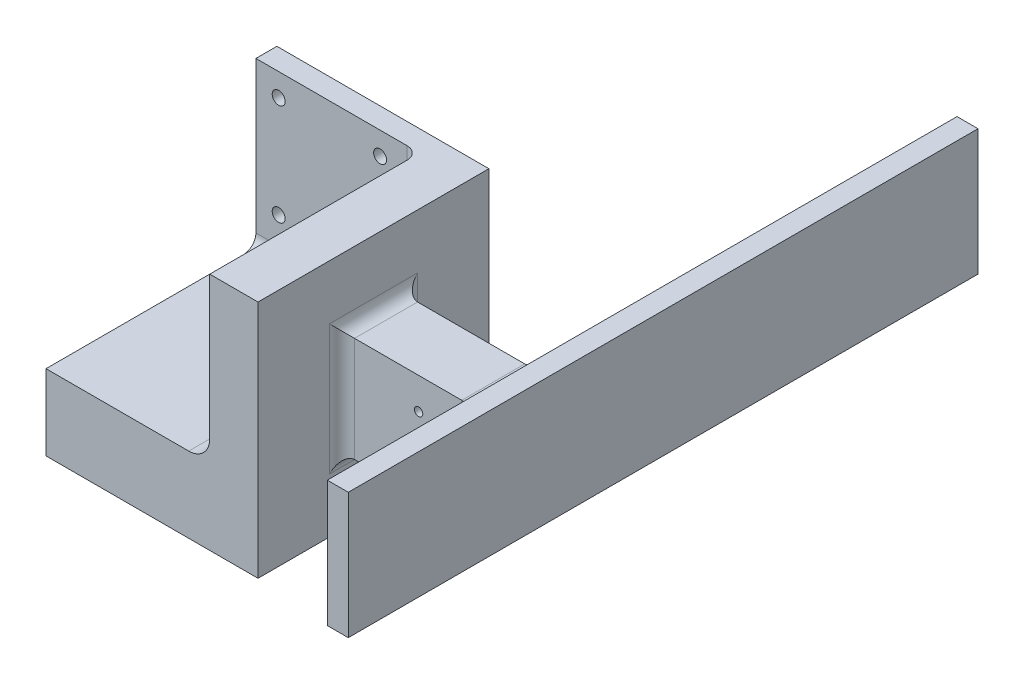
SolidWorks part; units mm, degrees
ref_plane "Front Plane" through (0, 0, 0) normal (0, 0, 1) x (1, 0, 0)
ref_plane "Top Plane" through (0, 0, 0) normal (0, 1, 0) x (1, 0, 0)
ref_plane "Right Plane" through (0, 0, 0) normal (1, 0, 0) x (0, 0, -1)
sketch "Sketch1" plane through (0, 0, 0) normal (0, 0, 1) x (1, 0, 0)
  line L0 (0, 36.3302) -> (0, -35.4873) construction
  line L1 (-17.5, 17.5) -> (17.5, 17.5)
  line L2 (-17.5, 17.5) -> (-17.5, -17.5)
  line L5 (-17.5, 17.5) -> (17.5, -17.5) construction
  line L6 (-17.5, -17.5) -> (17.5, 17.5) construction
  line L7 (-46.7825, 0) -> (42.7365, 0) construction
  line L8 (-17.5, -17.5) -> (-17.5, -21.5)
  line L9 (-17.5, -21.5) -> (17.5, -21.5)
  line L11 (17.5, 17.5) -> (21.5, 17.5)
  line L12 (21.5, 17.5) -> (21.5, -21.5)
  line L13 (21.5, -21.5) -> (17.5, -21.5)
  circle A0 centre (-12.0784, 12.0784) radius 1.542
  circle A1 centre (12.0784, 12.0784) radius 1.542
  circle A2 centre (12.0784, -12.0784) radius 1.542
  circle A3 centre (-12.0784, -12.0784) radius 1.542
  point P0 (0, 0)
  dimension "D1" = 90
  dimension "D2" = 17.0815
  dimension "D3" = 35
  dimension "D4" = 4
  dimension "D6" = 4
extrude "Boss-Extrude1" add sketch "Sketch1" along normal blind 5
sketch "Sketch4" plane through (0, 0, 5) normal (0, 0, 1) x (1, 0, 0)
  line L0 (21.5, 17.5) -> (26, 17.5)
  line L1 (26, 17.5) -> (26, -26)
  line L2 (26, -26) -> (-17.5, -26)
  line L3 (-17.5, -26) -> (-17.5, -21.5)
  line L4 (-17.5, -21.5) -> (21.5, -21.5)
  line L5 (21.5, -21.5) -> (21.5, 17.5)
  dimension "D1" = 4.5
  dimension "D2" = 4.5
extrude "Boss-Extrude4" add sketch "Sketch4" along normal blind 50 and the other way through all
fillet "Fillet3" radius 3 2 edges at (2, -21.5, 5) (21.5, -2, 5)
fillet "Fillet4" radius 5 2 edges at (20.6213, -20.6213, 5.8787) (21.5, -21.5, 31.5)
sketch "Sketch6" plane through (0, 0, 55) normal (0, 0, 1) x (1, 0, 0)
  line L0 (-17.5, -26) -> (26, -26)
  line L2 (26, -39.5) -> (-17.5, -39.5)
  line L3 (-17.5, -39.5) -> (-17.5, -26)
  line L4 (26, 17.5) -> (33, 17.5)
  line L5 (33, 17.5) -> (33, -39.5)
  line L6 (33, -39.5) -> (26, -39.5)
  line L7 (26, 17.5) -> (26, -26)
  dimension "D1" = 13.5
  dimension "D2" = 7
extrude "Boss-Extrude5" add sketch "Sketch6" against normal through all
sketch "Sketch7" plane through (33, 0, 0) normal (1, 0, 0) x (0, 0, -1)
  line L0 (-27.5, 17.5) -> (-27.5, -39.5) construction
  line L1 (-35, 1.5) -> (-20, 1.5)
  line L2 (-35, 1.5) -> (-35, -23.5)
  line L3 (-35, -23.5) -> (-20, -23.5)
  line L4 (-20, 1.5) -> (-20, -23.5)
  line L5 (-35, 1.5) -> (-20, -23.5) construction
  line L6 (-35, -23.5) -> (-20, 1.5) construction
  line L7 (0, 17.5) -> (-55, 17.5) construction
  line L8 (0, -39.5) -> (-55, -39.5) construction
  line L9 (-55, -11) -> (0, -11) construction
  line L10 (-55, -39.5) -> (-55, 17.5) construction
  line L11 (0, -39.5) -> (0, 17.5) construction
  point P0 (-27.5, -11)
  dimension "D1" = 15
  dimension "D2" = 25
extrude "Boss-Extrude6" add sketch "Sketch7" along normal blind 36.5
sketch "Sketch8" plane through (0, 0, 35) normal (0, 0, 1) x (1, 0, 0)
  line L0 (51.25, 1.5) -> (51.25, -23.5) construction
  line L1 (69.5, 1.5) -> (33, 1.5) construction
  line L2 (69.5, -23.5) -> (33, -23.5) construction
  circle A0 centre (51.25, -11) radius 1
  circle A1 centre (51.25, -16) radius 1
  circle A2 centre (51.25, -6) radius 1
  dimension "D1" = 5
  dimension "D2" = 5
extrude "Cut-Extrude1" cut sketch "Sketch8" against normal through all
sketch "Sketch9" plane through (69.5, 0, 0) normal (1, 0, 0) x (0, 0, -1)
  line L0 (-35, -11) -> (-78.9945, -11) construction
  line L1 (-70, 4) -> (80, 4)
  line L2 (-70, 4) -> (-70, -26)
  line L3 (-70, -26) -> (80, -26)
  line L4 (80, 4) -> (80, -26)
  line L5 (-35, 1.5) -> (-35, -23.5) construction
  dimension "D1" = 150
  dimension "D2" = 35
  dimension "D3" = 30
extrude "Boss-Extrude7" add sketch "Sketch9" against normal blind 5
fillet "Fillet5" radius 3 4 edges at (64.5, -23.5, 27.5) (64.5, -11, 20) (64.5, 1.5, 27.5) (64.5, -11, 35)
fillet "Fillet6" radius 3 4 edges at (33, -23.5, 27.5) (33, -11, 20) (33, 1.5, 27.5) (33, -11, 35)
